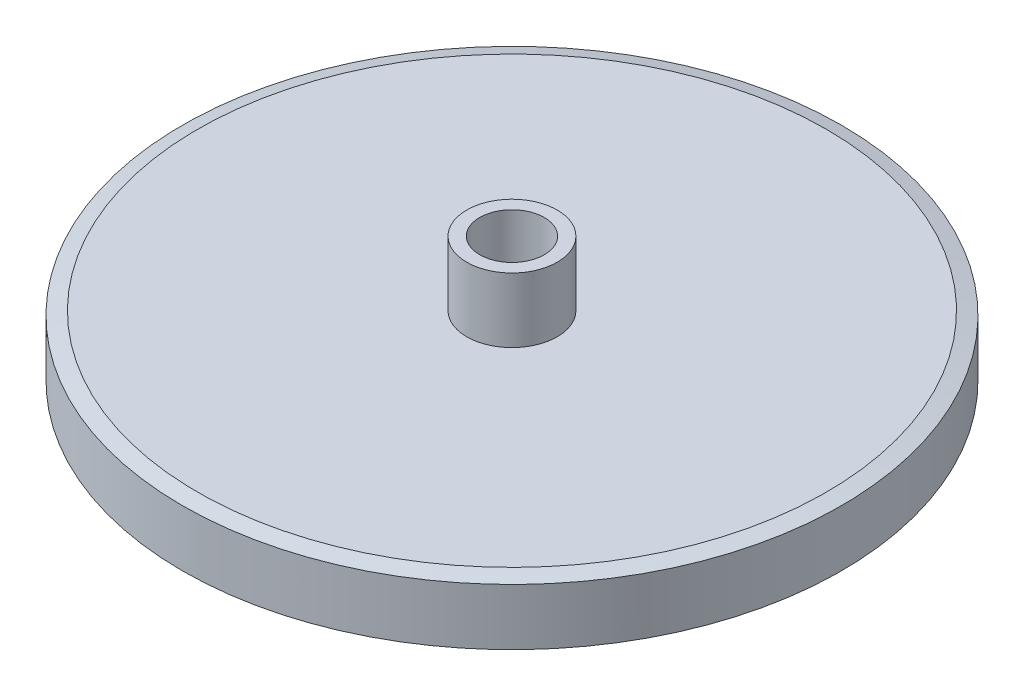
SolidWorks part; units mm, degrees
material "Сталь ШХ15 ГОСТ 801-78"
ref_plane "Plane1" through (0, 0, 0) normal (0, 0, 1) x (1, 0, 0)
ref_plane "Plane2" through (0, 0, 0) normal (0, 1, 0) x (1, 0, 0)
ref_plane "Plane3" through (0, 0, 0) normal (1, 0, 0) x (0, 0, -1)
sketch "Эскиз1" plane through (0, 0, 0) normal (0, 0, 1) x (1, 0, 0)
  line L0 (0, 0) -> (25.5, 0)
  line L1 (25.5, 0) -> (25.5, 5)
  line L2 (25.5, 5) -> (3.5, 5)
  line L3 (3.5, 5) -> (3.5, 10)
  line L4 (3.5, 10) -> (0, 10)
  line L5 (0, 10) -> (0, 0)
  dimension "D1" = 5
  dimension "30" = 25.5
  dimension "D3" = 3.5
  dimension "D4" = 5
ref_axis "Ось1" through (0, 10, 0) along (0, -1, 0)
revolve "Повернуть2" add sketch "Эскиз1" angle 360 about axis through (0, 10, 0) along (0, -1, 0)
chamfer "Фаска1" distance 1.175 angle 15 1 edges at (0, 5, 25.5) first distance on face at (0, 5, 3.5)
sketch "Эскиз2" plane through (0, 0, 0) normal (0, -1, 0) x (-1, 0, 0)
  circle A0 centre (0, 0) radius 2.5
sketch "Эскиз3" plane through (0, 0, 0) normal (1, 0, 0) x (0, 0, -1)
  circle A0 centre (0, 7.4791) radius 1
extrude "Вырез-Вытянуть3" cut sketch "Эскиз2" against normal through all both
chamfer "Фаска2" distance 1.175 angle 15 1 edges at (0, 0, 25.5) first distance on face at (0, 0, -2.5)
